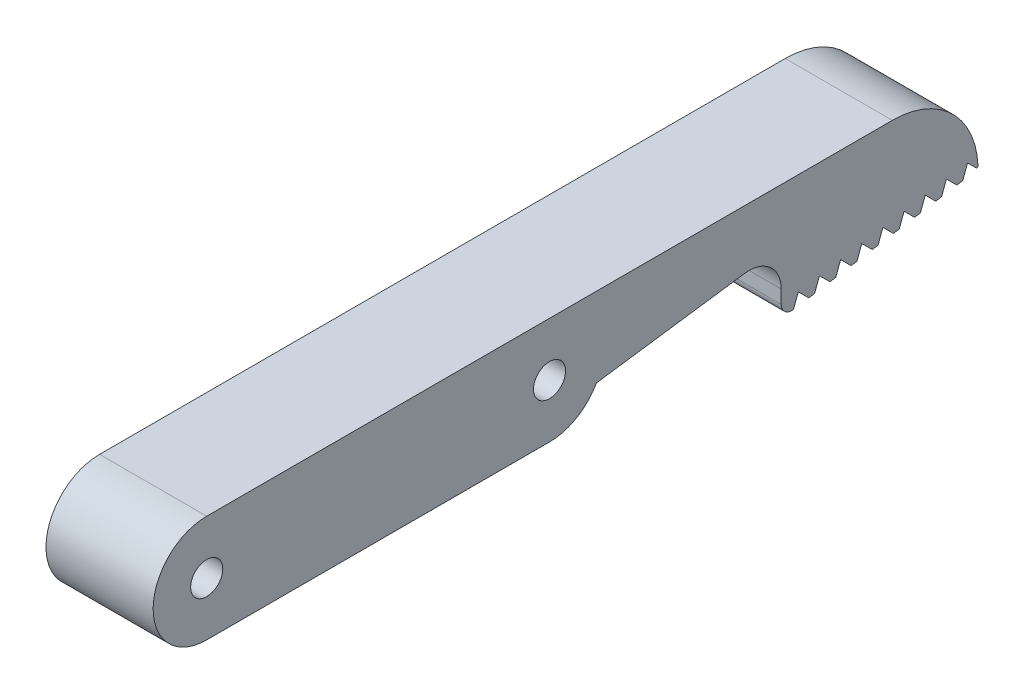
SolidWorks part; units mm, degrees
ref_plane "Front" through (0, 0, 0) normal (0, 0, 1) x (1, 0, 0)
ref_plane "Top" through (0, 0, 0) normal (0, 1, 0) x (1, 0, 0)
ref_plane "Right" through (0, 0, 0) normal (1, 0, 0) x (0, 0, -1)
sketch "Sketch1" plane through (0, 0, 0) normal (1, 0, 0) x (0, 0, -1)
  line L1 (-16, -5) -> (16, -5)
  line L2 (-16, -5) -> (-16, 5) construction
  line L3 (-16, 5) -> (16, 5)
  line L4 (16, -5) -> (16, 5) construction
  line L5 (-16, -5) -> (16, 5) construction
  line L6 (-16, 5) -> (16, -5) construction
  circle A0 centre (16, 0) radius 5
  circle A1 centre (-16, 0) radius 5
  circle A2 centre (16, 0) radius 1.5
  circle A3 centre (-16, 0) radius 1.5
  point P0 (0, 0)
  dimension "D1" = 10
  dimension "D2" = 3
  dimension "D3" = 3
  dimension "D4" = 32
extrude "Boss-Extrude1" add sketch "Sketch1" along normal mid plane 10 contours A1 L1 A0 L3 | A1 A3 | A0 A2 region at (0, 0, 0) region at (0, 0, 20.8586) region at (0, 0, -11.1414)
sketch "Sketch6" plane through (5, 0, 0) normal (1, 0, 0) x (0, 0, -1)
  line L0 (20.3754, -2.4198) -> (37.6264, 0)
  line L1 (37.6264, 0) -> (37.6264, -5.8635)
  line L3 (56, -0.7886) -> (56, 5)
  line L4 (56, 5) -> (16, 5)
  line L7 (37.6264, -5.8635) -> (56, -2.9318)
  line L8 (56, -2.9318) -> (56, -0.7886)
  arc A0 (16, -5) -> (16, 5) centre (16, 0) ccw construction
  arc A1 (20.3754, -2.4198) -> (16, 5) centre (16, 0) ccw
  dimension "D1" = 40
  dimension "D2" = 5.8635
extrude "Boss-Extrude4" add sketch "Sketch6" against normal blind 10 contours A1 L4 L3 L8 L7 L1 L0
fillet "Fillet5" radius 3 1 edges at (0, 0, -37.6264)
fillet "Fillet7" radius 8 1 edges at (0, 5, -56)
sketch "Sketch8" plane through (5, 0, 0) normal (1, 0, 0) x (0, 0, -1)
  line L0 (56, -2.9318) -> (55.0201, -1.9519)
  line L1 (55.0201, -1.9519) -> (54.5704, -3.1599)
  line L3 (37.6264, -5.8635) -> (56, -2.9318) construction
  line L4 (53.0451, -2.267) -> (52.5954, -3.475)
  line L5 (54.025, -3.2469) -> (53.0451, -2.267)
  line L6 (51.0701, -2.5822) -> (50.6204, -3.7901)
  line L7 (52.05, -3.562) -> (51.0701, -2.5822)
  line L8 (49.0951, -2.8973) -> (48.6453, -4.1053)
  line L9 (50.075, -3.8772) -> (49.0951, -2.8973)
  line L10 (47.1201, -3.2124) -> (46.6703, -4.4204)
  line L11 (48.0999, -4.1923) -> (47.1201, -3.2124)
  line L12 (45.1451, -3.5276) -> (44.6953, -4.7356)
  line L13 (46.1249, -4.5075) -> (45.1451, -3.5276)
  line L14 (43.17, -3.8427) -> (42.7203, -5.0507)
  line L15 (44.1499, -4.8226) -> (43.17, -3.8427)
  line L16 (41.195, -4.1579) -> (40.7453, -5.3658)
  line L17 (42.1749, -5.1377) -> (41.195, -4.1579)
  line L18 (39.22, -4.473) -> (38.7703, -5.681)
  line L19 (40.1999, -5.4529) -> (39.22, -4.473)
  line L20 (38.7703, -5.681) -> (37.6264, -5.8635)
  line L21 (37.6264, -5.8635) -> (46.1249, -12.9606)
  line L22 (46.1249, -12.9606) -> (56, -2.9318)
  line L23 (40.1999, -5.4529) -> (40.7453, -5.3658)
  line L24 (42.1749, -5.1377) -> (42.7203, -5.0507)
  line L25 (44.1499, -4.8226) -> (44.6953, -4.7356)
  line L26 (46.1249, -4.5075) -> (46.6703, -4.4204)
  line L27 (48.0999, -4.1923) -> (48.6453, -4.1053)
  line L28 (50.075, -3.8772) -> (50.6204, -3.7901)
  line L29 (52.05, -3.562) -> (52.5954, -3.475)
  line L30 (54.025, -3.2469) -> (54.5704, -3.1599)
  dimension "D1" = 9
extrude "Cut-Extrude6" cut sketch "Sketch8" against normal blind 10
fillet "Fillet9" radius 1 1 edges at (0, -5.8635, -37.6264)
fillet "Fillet11" radius 0.1 1 edges at (0, -2.9318, -56)
